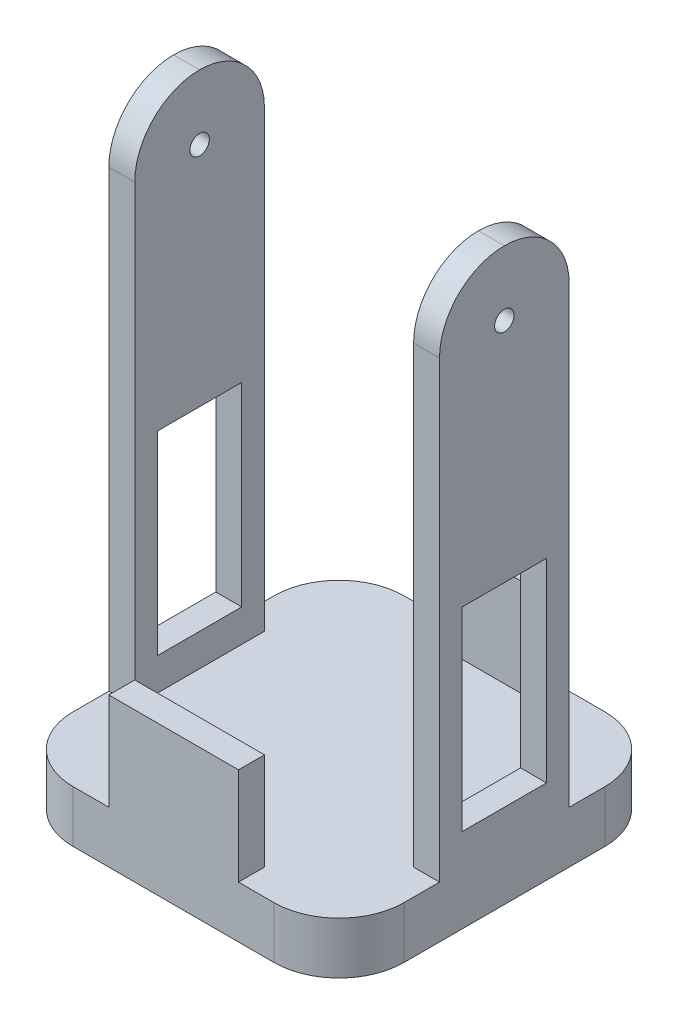
SolidWorks part; units mm, degrees
ref_plane "Plano frontal" through (0, 0, 0) normal (0, 0, 1) x (1, 0, 0)
ref_plane "Plano superior" through (0, 0, 0) normal (0, 1, 0) x (1, 0, 0)
ref_plane "Plano direito" through (0, 0, 0) normal (1, 0, 0) x (0, 0, -1)
sketch "Esboço1" plane through (0, 0, 0) normal (0, 1, 0) x (1, 0, 0)
  line L1 (-25.5, -25.5) -> (25.5, -25.5)
  line L2 (-25.5, -25.5) -> (-25.5, 25.5)
  line L3 (-25.5, 25.5) -> (25.5, 25.5)
  line L4 (25.5, -25.5) -> (25.5, 25.5)
  line L5 (-25.5, -25.5) -> (25.5, 25.5) construction
  line L6 (-25.5, 25.5) -> (25.5, -25.5) construction
  point P0 (0, 0)
  dimension "D1" = 51
  dimension "D2" = 51
extrude "Ressalto-extrusão1" add sketch "Esboço1" along normal blind 8
sketch "Esboço2" plane through (0, 8, 0) normal (0, 1, 0) x (1, 0, 0)
  line L5 (-25.5, 25.5) -> (-25.5, -25.5) construction
  line L10 (25.5, 25.5) -> (-25.5, 25.5) construction
  line L11 (-25.5, 10) -> (-21.5, 10)
  line L12 (-25.5, 10) -> (-25.5, -10)
  line L13 (-25.5, -10) -> (-21.5, -10)
  line L14 (-21.5, 10) -> (-21.5, -10)
  line L15 (0, 0) -> (0, 25.5) construction
  line L16 (25.5, -10) -> (21.5, -10)
  line L17 (21.5, 10) -> (21.5, -10)
  line L18 (25.5, 10) -> (21.5, 10)
  line L19 (25.5, 10) -> (25.5, -10)
  dimension "D1" = 20
  dimension "D2" = 15.5
  dimension "D3" = 4
extrude "Ressalto-extrusão2" add sketch "Esboço2" along normal blind 80
sketch "Esboço4" plane through (0, 8, 0) normal (0, 1, 0) x (1, 0, 0)
  line L0 (25.5, 25.5) -> (-25.5, 25.5) construction
  line L1 (-10, 25.5) -> (10, 25.5)
  line L2 (-10, 25.5) -> (-10, 21.5)
  line L3 (-10, 21.5) -> (10, 21.5)
  line L4 (10, 25.5) -> (10, 21.5)
  line L5 (-25.5, 25.5) -> (-25.5, 10) construction
  line L9 (0, 0) -> (-25.5, 0) construction
  line L10 (-25.5, 10) -> (-25.5, -10) construction
  line L11 (-10, -21.5) -> (10, -21.5)
  line L12 (10, -25.5) -> (10, -21.5)
  line L13 (-10, -25.5) -> (10, -25.5)
  line L14 (-10, -25.5) -> (-10, -21.5)
  dimension "D1" = 15.5
  dimension "D2" = 20
  dimension "D3" = 4
extrude "Ressalto-extrusão3" add sketch "Esboço4" along normal blind 15
sketch "Esboço5" plane through (0, 0, 0) normal (0, -1, 0) x (1, 0, 0)
  line L0 (0, 25.5) -> (0, -25.5) construction
  line L1 (-25.5, 25.5) -> (25.5, 25.5) construction
  line L2 (25.5, -25.5) -> (-25.5, -25.5) construction
  line L3 (-25.5, 0) -> (25.5, 0) construction
  line L4 (-25.5, -25.5) -> (-25.5, 25.5) construction
  line L5 (25.5, 25.5) -> (25.5, -25.5) construction
  line L6 (-25.5, 25.5) -> (25.5, -25.5) construction
  circle A0 centre (-11, 11) radius 1.6
  circle A1 centre (11, 11) radius 1.6
  circle A2 centre (11, -11) radius 1.6
  circle A3 centre (-11, -11) radius 1.6
  dimension "D1" = 3.2
  dimension "D2" = 11
extrude "Corte-extrusão2" cut sketch "Esboço5" against normal blind 7
fillet "Filete2" radius 10 4 edges at (-25.5, 4, -25.5) (25.5, 4, -25.5) (-25.5, 4, 25.5) (25.5, 4, 25.5)
sketch "Esboço6" plane through (-25.5, 0, 0) normal (-1, 0, 0) x (0, 0, 1)
  line L0 (0, 0) -> (0, 88) construction
  line L1 (-10, 88) -> (10, 88) construction
  line L7 (10, 13) -> (-10, 13) construction
  line L8 (10, 88) -> (10, 8) construction
  line L9 (-10, 8) -> (10, 8) construction
  line L10 (-10, 88) -> (-10, 8) construction
  line L16 (-6.5, 43) -> (6.5, 43)
  line L17 (-6.5, 43) -> (-6.5, 13)
  line L18 (-6.5, 13) -> (6.5, 13)
  line L19 (6.5, 43) -> (6.5, 13)
  line L20 (-6.5, 43) -> (6.5, 13) construction
  line L21 (-6.5, 13) -> (6.5, 43) construction
  point P15 (0, 28)
  dimension "D1" = 5
  dimension "D2" = 13
  dimension "D3" = 30
extrude "Corte-extrusão3" cut sketch "Esboço6" against normal through all and the other way through all
sketch "Esboço7" plane through (25.5, 0, 0) normal (1, 0, 0) x (0, 0, -1)
  line L0 (0, 88) -> (0, 43) construction
  line L1 (-10, 88) -> (10, 88) construction
  line L2 (-6.5, 43) -> (6.5, 43) construction
  circle A0 centre (0, 78) radius 1.5
  dimension "D1" = 3
  dimension "D2" = 10
extrude "Corte-extrusão4" cut sketch "Esboço7" against normal through all
fillet "Filete6" radius 10 4 edges at (23.5, 88, -10) (23.5, 88, 10) (-23.5, 88, -10) (-23.5, 88, 10)
